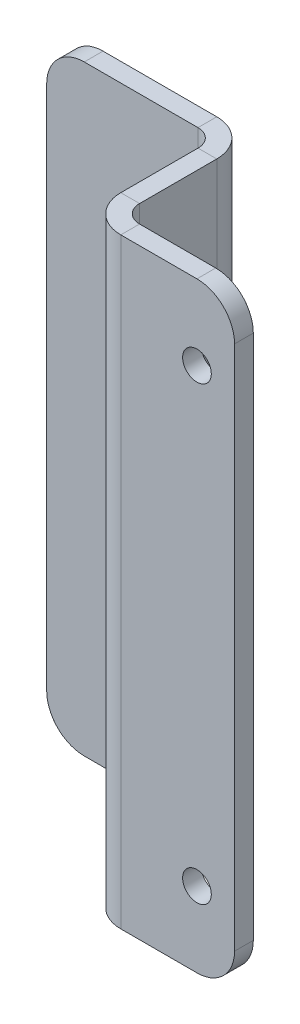
SolidWorks part; units mm, degrees
note: The reader was unsure of these and kept them because the rebuilt part matched: flange length of "Edge-Flange1", "Edge-Flange2".
ref_plane "Front Plane" through (0, 0, 0) normal (0, 0, 1) x (1, 0, 0)
ref_plane "Top Plane" through (0, 0, 0) normal (0, 1, 0) x (1, 0, 0)
ref_plane "Right Plane" through (0, 0, 0) normal (1, 0, 0) x (0, 0, -1)
sketch "Sketch1" plane through (0, 0, 0) normal (0, 0, 1) x (1, 0, 0)
  line L1 (0, 0) -> (-25.4, 0)
  line L2 (0, 0) -> (0, -101.6)
  line L3 (0, -101.6) -> (-25.4, -101.6)
  line L4 (-25.4, 0) -> (-25.4, -101.6)
  dimension "D1" = 25.4
  dimension "D2" = 101.6
base flange "Base-Flange1" sketch "Sketch1" thickness 3.175 reverse thickness direction no parameters "D1"=3
edge flange "Edge-Flange1" sketch "Sketch8" flange angle 90 flange length 22.225 flange position material inside bend radius 3 thickness 3.175 relief rectangular parameters "D6"=10
sketch "Sketch8" plane through (-25.4, 0, -3.175) normal (-1, 0, 0) x (0, 1, 0)
  line L0 (0, 0) -> (-101.6, 0) construction
  line L1 (0, 0) -> (-101.6, 0)
  line L2 (-101.6, 0) -> (-101.6, 19.05)
  line L3 (-101.6, 19.05) -> (0, 19.05)
  line L4 (0, 19.05) -> (0, 0)
bend "EdgeBend1" bend radius 3 bend angle 90 parameters "D5"=1
edge flange "Edge-Flange2" sketch "Sketch11" flange angle 90 flange length 31.75 flange position material outside bend radius 3 thickness 3.175 relief rectangular parameters "D6"=10
sketch "Sketch11" plane through (-25.4, 0, -22.225) normal (0, 0, 1) x (0, 1, 0)
  line L2 (-101.6, 0) -> (-101.6, 28.575)
  line L3 (-101.6, 28.575) -> (0, 28.575)
  line L4 (0, 28.575) -> (0, 0)
  line L5 (0, 0) -> (-101.6, 0) construction
  line L6 (0, 0) -> (-101.6, 0)
bend "EdgeBend2" bend radius 3 bend angle 90 parameters "D5"=2
hole_wizard "#11 (0.191) Diameter Hole1" positions "Sketch14" profile "Sketch15" hole size "#11" standard "ANSI Inch" end condition through all
sketch "Sketch14" plane through (0, 0, 0) normal (0, 0, 1) x (1, 0, 0)
  line L0 (0, -101.6) -> (0, 0) construction
  line L1 (0, 0) -> (-19.225, 0) construction
  line L2 (-19.225, -101.6) -> (0, -101.6) construction
  point P0 (-6.35, -12.7)
  point P2 (-6.35, -88.9)
  dimension "D1" = 6.35
  dimension "D2" = 12.7
  dimension "D3" = 12.7
sketch "Sketch15" plane through (-6.35, -12.7, 0) normal (1, 0, 0) x (0, -1, 0)
  line L0 (0, 0) -> (0, 25.4)
  line L1 (0, 25.4) -> (2.4257, 25.4)
  line L2 (2.4257, 25.4) -> (2.4257, 0)
  line L5 (2.4257, 0) -> (0, 0)
  line L11 (0, -6.35) -> (0, 107.95) construction
  dimension "Thru Hole Dia." = 4.8514
  dimension "Thru Hole Depth" = 25.4
fillet "Fillet1" radius 6.35 4 edges at (-53.975, 0, -23.8125) (-53.975, -101.6, -23.8125) (0, -101.6, -1.5875) (0, 0, -1.5875)
sketch "Bend-Lines1" [suppressed] plane through (0, 0, 0) normal (0, 1, 0) x (1, 0, 0)
sketch "Bounding-Box1" [suppressed] plane through (0, 0, 0) normal (0, 1, 0) x (1, 0, 0)
sheet metal parameters "Sheet-Metal1" thickness 3.175 parameters "D1"=3
flat pattern "Flat-Pattern1" [suppressed]
sketch "Bend-Lines2" plane through (0, 0, 0) normal (0, 1, 0) x (1, 0, 0)
sketch3d "Bounding-Box2" [suppressed]
  line L0 (0, 0, 0) -> (0, -152.4, 0) construction
  line L1 (38.1, 0, 0) -> (38.1, -152.4, 0) construction
  line L2 (0, 0, 0) -> (38.1, 0, 0) construction
  line L3 (0, -152.4, 0) -> (38.1, -152.4, 0) construction
sheet metal parameters "Sheet-Metal2" thickness 3.175 parameters "D1"=3
flat pattern "Flat-Pattern1"
sketch "Bend-Lines2" plane through (0, 0, 0) normal (0, 0, 1) x (1, 0, 0)
  line L0 (-35.528, 0) -> (-35.528, -152.4) construction
  line L1 (-35.528, 0) -> (-35.528, -152.4) construction
sketch3d "Bounding-Box2" [suppressed]
  line L0 (0, 0, 0) -> (0, -152.4, 0) construction
  line L1 (-53.5935, 0, 0) -> (-53.5935, -152.4, 0) construction
  line L2 (0, 0, 0) -> (-53.5935, 0, 0) construction
  line L3 (0, -152.4, 0) -> (-53.5935, -152.4, 0) construction
bend of the flat pattern "Flatten-<EdgeBend1>1"
sheet metal parameters "Sheet-Metal3" thickness 3.175 parameters "D1"=3
flat pattern "Flat-Pattern1"
sketch "Bend-Lines2" plane through (0, 0, 0) normal (0, 0, 1) x (1, 0, 0)
  line L0 (-35.528, 0) -> (-35.528, -152.4) construction
  line L1 (-35.528, 0) -> (-35.528, -152.4) construction
  line L2 (-54.1965, 0) -> (-54.1965, -152.4) construction
  line L3 (-54.1965, 0) -> (-54.1965, -152.4) construction
sketch3d "Bounding-Box2" [suppressed]
  line L0 (0, 0, 0) -> (0, -152.4, 0) construction
  line L1 (-96.0746, 0, 0) -> (-96.0746, -152.4, 0) construction
  line L2 (0, 0, 0) -> (-96.0746, 0, 0) construction
  line L3 (0, -152.4, 0) -> (-96.0746, -152.4, 0) construction
bend of the flat pattern "Flatten-<EdgeBend1>1"
bend of the flat pattern "Flatten-<EdgeBend2>1"
sheet metal parameters "Sheet-Metal5" thickness 3.175 parameters "D1"=3
flat pattern "Flat-Pattern1"
sketch "Bend-Lines2" plane through (0, 0, 0) normal (0, 0, 1) x (1, 0, 0)
  line L0 (-22.828, 0) -> (-22.828, -101.6) construction
  line L1 (-22.828, 0) -> (-22.828, -101.6) construction
  line L2 (-43.084, 0) -> (-43.084, -101.6) construction
  line L3 (-43.084, 0) -> (-43.084, -101.6) construction
sketch3d "Bounding-Box2" [suppressed]
  line L0 (0, -101.6, 0) -> (0, 0, 0) construction
  line L1 (-72.2621, -101.6, 0) -> (-72.262, 0, 0) construction
  line L2 (0, -101.6, 0) -> (-72.2621, -101.6, 0) construction
  line L3 (0, 0, 0) -> (-72.262, 0, 0) construction
bend of the flat pattern "Flatten-<EdgeBend1>1"
bend of the flat pattern "Flatten-<EdgeBend2>1"
